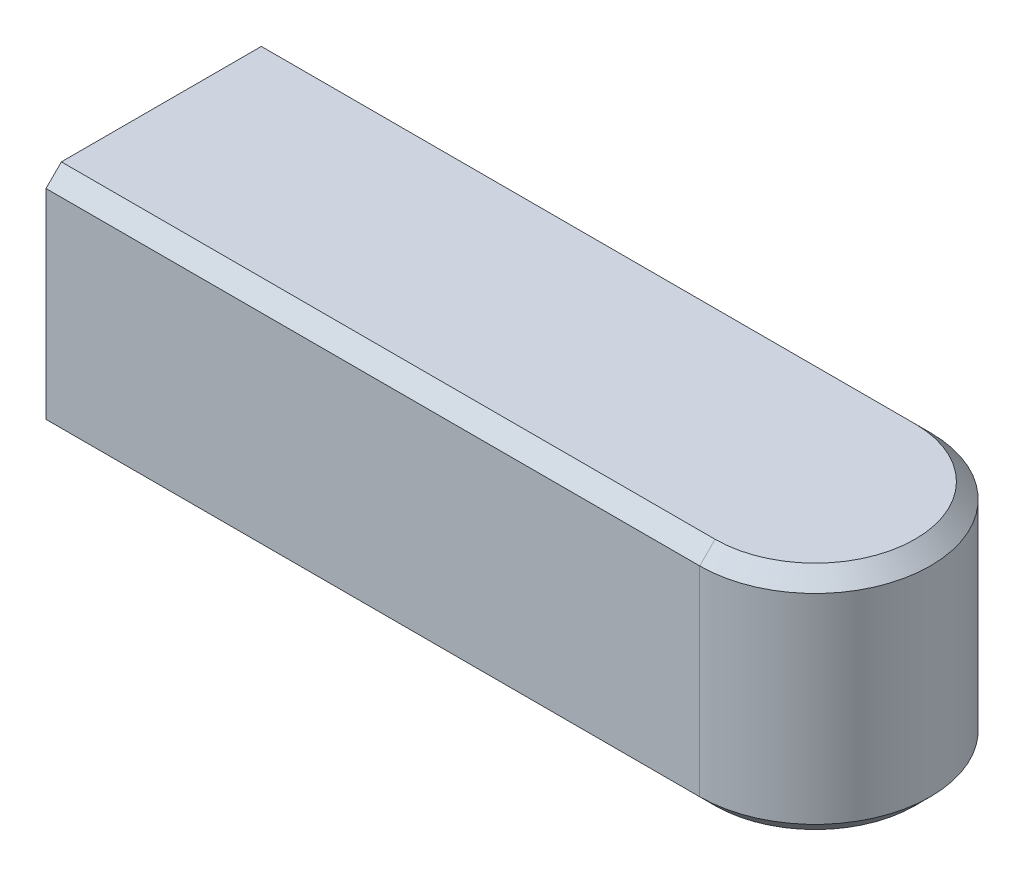
SolidWorks part; units mm, degrees
material "S45C"
ref_plane "Front Plane" through (0, 0, 0) normal (0, 0, 1) x (1, 0, 0)
ref_plane "Top Plane" through (0, 0, 0) normal (0, 1, 0) x (1, 0, 0)
ref_plane "Right Plane" through (0, 0, 0) normal (1, 0, 0) x (0, 0, -1)
sketch "Sketch1" plane through (0, 0, 0) normal (0, 1, 0) x (1, 0, 0)
  line L0 (-5, 0) -> (5, 0) construction
  line L1 (0, 1.5) -> (0, -1.5) construction
  line L3 (-5, 1.5) -> (5, 1.5)
  line L4 (-5, 1.5) -> (-5, -1.5)
  line L5 (-5, -1.5) -> (5, -1.5)
  line L6 (5, 1.5) -> (5, -1.5)
  dimension "L" = 10
  dimension "B" = 3
extrude "Boss-Extrude1" add sketch "Sketch1" along normal blind 3
chamfer "Chamfer1" [suppressed] distance 0.2 angle 45
fillet "Fillet1" [suppressed] type full round
fillet "Fillet2" 2 edges at (5, 1.5, 1.5) (5, 1.5, -1.5) type full round first side face at (0, 1.5, 1.5) second side face at (0, 1.5, -1.5) middle face at (5, 1.5, 0)
chamfer "Chamfer2" distance 0.2 angle 45 6 edges at (-0.75, 0, -1.5) (5, 0, 0) (-0.75, 0, 1.5) (-0.75, 3, -1.5) (5, 3, 0) (-0.75, 3, 1.5)
